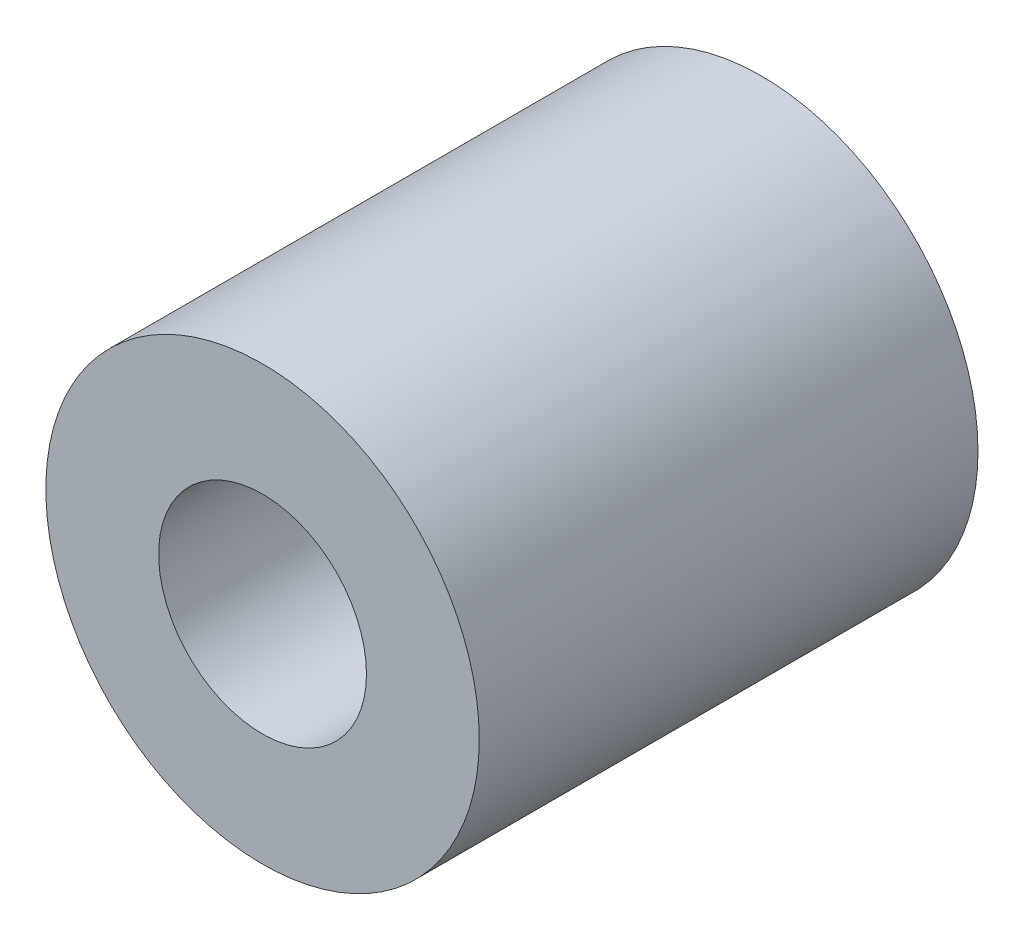
SolidWorks part; units mm, degrees
ref_plane "Front Plane" through (0, 0, 0) normal (0, 0, 1) x (1, 0, 0)
ref_plane "Top Plane" through (0, 0, 0) normal (0, 1, 0) x (1, 0, 0)
ref_plane "Right Plane" through (0, 0, 0) normal (1, 0, 0) x (0, 0, -1)
sketch "Sketch2" plane through (0, 0, 0) normal (0, 0, 1) x (1, 0, 0)
  circle A2 centre (0, 0) radius 43.65 construction
  circle A3 centre (0, 0) radius 43.65 construction
  circle A4 centre (0, 0) radius 43.45
  circle A7 centre (0, 0) radius 20.8375
  circle A8 centre (0, 0) radius 20.6375 construction
  circle A9 centre (0, 0) radius 20.6375 construction
  dimension "D1" = 0.2
  dimension "D2" = 0.2
extrude "Boss-Extrude1" add sketch "Sketch2" along normal blind 100
